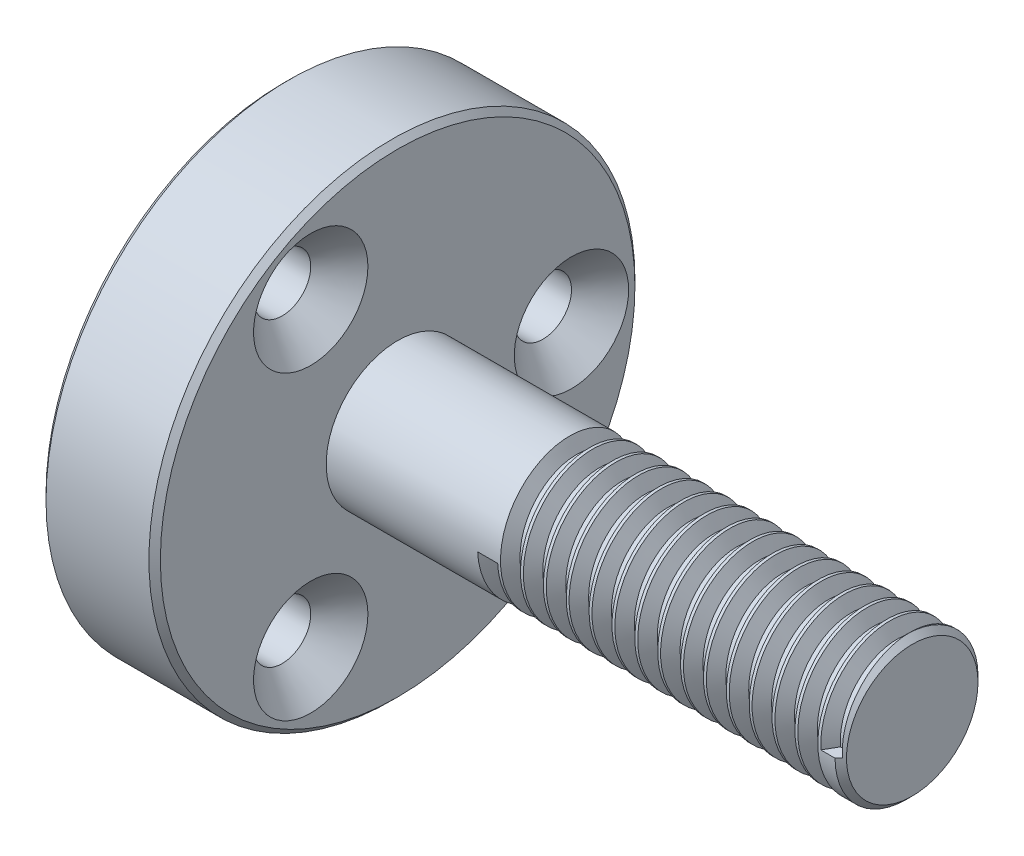
SolidWorks part; units mm, degrees
ref_plane "Front" through (0, 0, 0) normal (0, 0, 1) x (1, 0, 0)
ref_plane "Top" through (0, 0, 0) normal (0, 1, 0) x (1, 0, 0)
ref_plane "Right" through (0, 0, 0) normal (1, 0, 0) x (0, 0, -1)
sketch "Sketch1" plane through (0, 0, 0) normal (0, 0, 1) x (1, 0, 0)
  line L0 (0, 0) -> (-12.4233, 0) construction
  line L1 (-2.3, 4.5) -> (-2.3, 8.5)
  line L2 (-2.3, 8.5) -> (1.7, 8.5)
  line L3 (1.7, 8.5) -> (1.7, 2.5)
  line L4 (1.7, 2.5) -> (19.7, 2.5)
  line L5 (19.7, 2.5) -> (19.7, 0)
  line L6 (19.7, 0) -> (0, 0)
  line L7 (-2.3, 4.5) -> (0, 4.5)
  line L8 (0, 4.5) -> (0, 0)
  dimension "D1" = 9
  dimension "D2" = 17
  dimension "D3" = 17
  dimension "D4" = 17
  dimension "D5" = 4
  dimension "D6" = 2.3
  dimension "D7" = 18
  dimension "D8" = 5
revolve "Revolve1" add sketch "Sketch1" angle 360 about L0
sketch "Sketch2" plane through (-2.3, 0, 0) normal (-1, 0, 0) x (0, 0, 1)
  line L0 (0, 0) -> (-8.5, 0) construction
  line L1 (-5.214, -0.5) -> (2.174, -4.7654) construction
  line L2 (3.906, -5.7654) -> (-6.946, 0.5) construction
  circle A0 centre (0, 0) radius 8.5 construction
  circle A1 centre (0, 0) radius 1.7337 construction
  circle A2 centre (-6.08, 0) radius 1
  circle A3 centre (3.04, 5.2654) radius 1
  circle A4 centre (3.04, -5.2654) radius 1
  circle A5 centre (0, 0) radius 6.08 construction
  point P14 (0, 0)
  dimension "D1" = 2
  dimension "D2" = 12.16
extrude "Cut-Extrude1" cut sketch "Sketch2" against normal blind 10
chamfer "Chamfer1" distance 1 angle 45 3 edges at (1.7, -5.2654, 2.04) (1.7, 0, -7.08) (1.7, 5.2654, 2.04)
chamfer "Chamfer2" distance 0.1 angle 45 1 edges at (-2.3, 0, -4.5)
thread "Thread1" pitch 0.8 method cut profile "Thread Profile1" start angle 0, offset 0, length 12, pitch 0.8, diameter 5
ref_plane "Plane1" through (19.7, 0, 2.5) normal (0, -1, 0) x (0, 0, 1)
sketch "Thread Profile1" plane through (19.7, 0, 2.5) normal (0, -1, 0) x (0, 0, 1)
  line L0 (0, 0) -> (0, 0.8) construction
  line L11 (0, 0) -> (0, 0.7)
  line L12 (0, 0.7) -> (-0.433, 0.45)
  line L13 (-0.433, 0.45) -> (-0.433, 0.25)
  line L15 (-0.433, 0.25) -> (0, 0)
  line L17 (-0.433, 0.35) -> (0, 0.35) construction
  point P2 (0, 0)
  dimension "Pitch" = 0.8
  dimension "Profile_Angle" = 60
  dimension "Profile_Land" = 0.2
  dimension "Profile_Height" = 0.433
chamfer "Chamfer3" distance 0.2 angle 45 1 edges at (19.7, 0, -2.5)
chamfer "Chamfer4" distance 0.2 angle 45 2 edges at (1.7, 0, -8.5) (-2.3, 0, -8.5)
